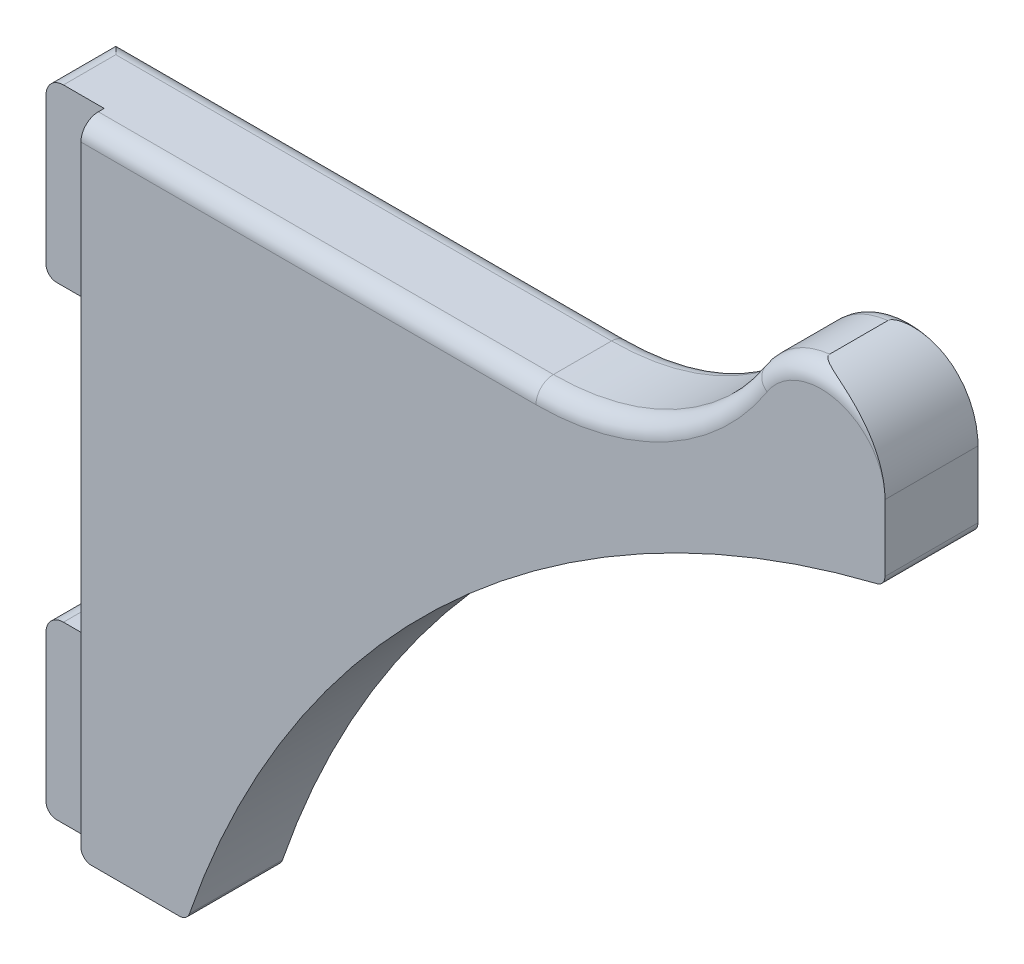
SolidWorks part; units mm, degrees
ref_plane "Plan de face" through (0, 0, 0) normal (0, 0, 1) x (1, 0, 0)
ref_plane "Plan de dessus" through (0, 0, 0) normal (0, 1, 0) x (1, 0, 0)
ref_plane "Plan de droite" through (0, 0, 0) normal (1, 0, 0) x (0, 0, -1)
sketch "Esquisse1" plane through (0, 0, 0) normal (0, 0, 1) x (1, 0, 0)
  line L0 (0, 0) -> (0, 9)
  line L1 (0, 9) -> (1, 9)
  line L4 (1, 0.0964) -> (10.1219, 0.0964)
  line L8 (10.1219, 55) -> (-4, 55)
  line L9 (1, 49) -> (0, 49)
  line L10 (0, 0) -> (-4, 0)
  line L11 (-4, 0) -> (-4, 15)
  line L12 (-4, 15) -> (1, 15)
  line L13 (1, 15) -> (1, 49)
  line L14 (0, 49) -> (0, 40)
  line L15 (0, 40) -> (-4, 40)
  line L16 (-4, 40) -> (-4, 55)
  line L17 (1, 9) -> (1, 0.0964)
  line L18 (10.1219, 55) -> (70.1219, 55) construction
  line L19 (10.1219, 55) -> (19.2932, 55)
  line L21 (60.4324, 68.4362) -> (70.1219, 68.4362)
  line L22 (70.1219, 68.4362) -> (70.1219, 55)
  line L25 (40.1219, 55) -> (19.2932, 55)
  arc A1 (40.1219, 55) -> (60.4324, 68.4362) centre (40.1219, 77.0691) ccw
  arc A3 (10.1219, 0.0964) -> (70.1219, 55) centre (89.4393, -26.3471) cw
  point P11 (0.5, 9)
  dimension "D1" = 40
  dimension "D2" = 1
  dimension "D3" = 1
  dimension "D4" = 15
  dimension "D5" = 15
  dimension "D6" = 4
  dimension "D7" = 4
  dimension "D8" = 6
  dimension "D9" = 6
  dimension "D10" = 60
extrude "Boss.-Extru.1" add sketch "Esquisse1" along normal mid plane 8
sketch "Esquisse4" plane through (0, 0, 4) normal (0, 0, 1) x (1, 0, 0)
  line L1 (0, 40) -> (-4, 40)
  line L2 (-4, 40) -> (-4, 55)
  line L3 (-4, 40) -> (-4, 55) construction
  line L5 (0, 0) -> (-4, 0)
  line L8 (-4, 0) -> (-4, 15) construction
  line L9 (-4, 15) -> (-4, 0)
  line L10 (-4, 55) -> (1, 55)
  line L11 (10.1219, 55) -> (-4, 55) construction
  line L13 (-4, 15) -> (1, 15)
  line L14 (-4, 15) -> (1, 15) construction
  line L16 (1, 55) -> (1, 40)
  line L17 (1, 40) -> (0, 40)
  line L18 (1, 15) -> (1, 0)
  line L19 (1, 0) -> (0, 0)
extrude "Enlèv. mat.-Extru.1" cut sketch "Esquisse4" against normal offset from surface (2 mm away) 6 up to face at (13.7538, 31.341, -4)
fillet "Congé4" radius 7 2 edges at (70.1219, 68.4362, 0) (60.4324, 68.4362, 0)
fillet "Congé3" radius 0.9 12 edges at (1, 0.0964, 0) (1, 9, -1) (0, 9, -1) (0, 0, -1) (-4, 0, -1) (1, 15, -1) (0, 40, -1) (-4, 40, -1) (1, 49, -1) (0, 49, -1) (70.1219, 55, 0) (10.1219, 0.0964, 0)
fillet "Congé5" radius 1.5 8 edges at (60.9383, 67.3839, -4) (50.7313, 57.7175, -4) (60.9383, 67.3839, 4) (50.7313, 57.7175, 4) (18.0609, 55, -4) (20.5609, 55, 4) (-4, 15, -1) (-4, 55, -1)
